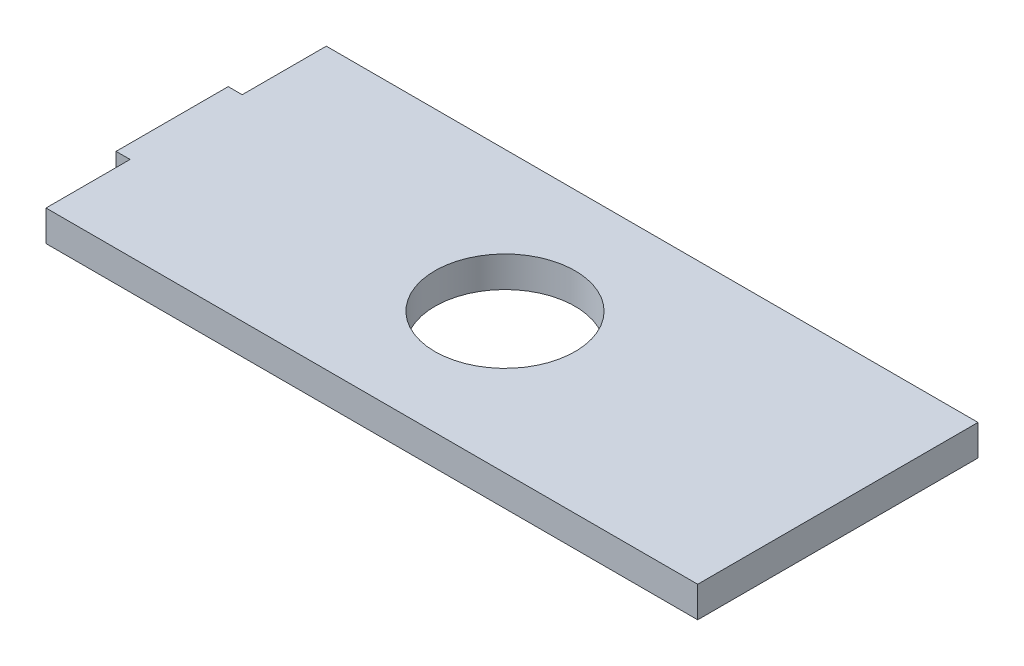
SolidWorks part; units mm, degrees
material "cardboard"
ref_plane "Front Plane" through (0, 0, 0) normal (0, 0, 1) x (1, 0, 0)
ref_plane "Top Plane" through (0, 0, 0) normal (0, 1, 0) x (1, 0, 0)
ref_plane "Right Plane" through (0, 0, 0) normal (1, 0, 0) x (0, 0, -1)
sketch "Sketch1" plane through (0, 0, 0) normal (0, 1, 0) x (1, 0, 0)
  line L0 (78.5546, 11.8659) -> (71.7044, 7.911)
  line L1 (104.0546, -12.1341) -> (110.9047, -8.1792)
  line L2 (119.2044, 7.911) -> (110.9047, 7.911)
  line L3 (119.2044, -8.1792) -> (110.9047, -8.1792)
  line L4 (71.7044, 7.911) -> (63.4047, 7.911)
  line L5 (126.0546, 11.8659) -> (119.2044, 7.911)
  line L6 (126.0546, -12.1341) -> (119.2044, -8.1792)
  line L7 (104.0546, 11.8659) -> (110.9047, 7.911)
  line L8 (126.0546, 11.8659) -> (138.8046, 11.8659)
  line L9 (126.0546, -12.1341) -> (162.8046, -12.1341)
  line L10 (56.5546, 11.8659) -> (63.4047, 7.911)
  line L11 (56.5546, -12.1341) -> (63.4047, -8.1792)
  line L12 (78.5546, -12.1341) -> (71.7044, -8.1792)
  line L13 (71.7044, -8.1792) -> (63.4047, -8.1792)
  line L14 (78.5546, 11.8659) -> (104.0546, 11.8659)
  line L15 (78.5546, -12.1341) -> (104.0546, -12.1341)
  line L16 (-11.1954, 77.6159) -> (-7.2405, 70.7658)
  line L17 (12.8046, 103.1159) -> (8.8496, 109.966)
  line L18 (-7.2405, 118.2658) -> (-7.2405, 109.966)
  line L19 (8.8496, 118.2658) -> (8.8496, 109.966)
  line L20 (-7.2405, 70.7658) -> (-7.2405, 62.466)
  line L21 (-11.1954, 125.1159) -> (-7.2405, 118.2658)
  line L22 (12.8046, 125.1159) -> (8.8496, 118.2658)
  line L23 (-11.1954, 103.1159) -> (-7.2405, 109.966)
  line L24 (-11.1954, 125.1159) -> (-11.1954, 137.8659)
  line L25 (12.8046, 125.1159) -> (12.8046, 161.8659)
  line L26 (-11.1954, 55.6159) -> (-7.2405, 62.466)
  line L27 (12.8046, 55.6159) -> (8.8496, 62.466)
  line L28 (12.8046, 77.6159) -> (8.8496, 70.7658)
  line L29 (8.8496, 70.7658) -> (8.8496, 62.466)
  line L30 (-11.1954, 77.6159) -> (-11.1954, 103.1159)
  line L31 (12.8046, 77.6159) -> (12.8046, 103.1159)
  line L32 (91.3046, 36.8659) -> (91.3046, 16.8659)
  line L33 (90.3046, 36.8659) -> (90.3046, 30.8659)
  line L34 (37.8046, 11.8659) -> (43.8046, 11.8659)
  line L35 (90.3046, 30.8659) -> (92.3046, 30.8659)
  line L36 (42.5546, 11.8659) -> (42.5546, 9.8659)
  line L37 (43.8046, 11.8659) -> (56.5546, 11.8659)
  line L38 (138.8046, 11.8659) -> (138.8046, -12.1341)
  line L39 (138.8046, 11.8659) -> (162.8046, 11.8659)
  line L40 (162.8046, 11.8659) -> (162.8046, 9.8659)
  line L41 (-27.6918, 14.2202) -> (0.8046, -14.2762)
  line L42 (-27.6918, 14.2202) -> (-13.5497, 28.3623)
  line L43 (0.8046, -14.2762) -> (14.9467, -0.1341)
  line L44 (-13.5497, 28.3623) -> (14.9467, -0.1341)
  line L45 (138.8046, 11.8659) -> (138.8046, 36.8659)
  line L46 (40.8046, 36.8659) -> (162.8046, 36.8659)
  line L47 (162.8046, 36.8659) -> (162.8046, 11.8659)
  line L48 (92.3046, 30.8659) -> (92.3046, 22.8659)
  line L49 (138.8046, 36.8659) -> (138.8046, 60.8659)
  line L50 (138.8046, 60.8659) -> (147.8046, 60.8659)
  line L51 (43.8046, 36.8659) -> (43.8046, 16.8659)
  line L52 (162.8046, 60.8659) -> (162.8046, 51.1879)
  line L53 (147.8046, 60.8659) -> (147.8046, 63.0659)
  line L54 (153.8046, 63.0659) -> (153.8046, 60.8659)
  line L55 (153.8046, 60.8659) -> (162.8046, 60.8659)
  line L56 (-58.1954, 137.8659) -> (-58.1954, 113.3659)
  line L57 (-38.1954, 113.3659) -> (-38.1954, 137.8659)
  line L58 (92.3046, 22.8659) -> (90.3046, 22.8659)
  line L59 (138.8046, -12.1341) -> (138.8046, -37.1341)
  line L60 (147.8046, -37.1341) -> (153.8046, -37.1341)
  line L61 (162.8046, -37.1341) -> (162.8046, -12.1341)
  line L62 (43.8046, -37.1341) -> (43.8046, -17.1341)
  line L63 (138.8046, -37.1341) -> (138.8046, -38.3141)
  line L64 (153.8046, -38.3141) -> (162.8046, -38.3141)
  line L65 (162.8046, -38.3141) -> (162.8046, -37.1341)
  line L66 (147.8046, -38.3141) -> (147.8046, -37.1341)
  line L67 (153.8046, -38.3141) -> (153.8046, -37.1341)
  line L68 (-37.3754, -138.1341) -> (-37.3754, -147.1341)
  line L69 (90.3046, 22.8659) -> (90.3046, 16.8659)
  line L70 (90.3046, 11.8659) -> (90.3046, 3.8659)
  line L71 (43.8046, -12.1341) -> (56.5546, -12.1341)
  line L72 (37.8046, -12.1341) -> (43.8046, -12.1341)
  line L73 (91.2784, 11.8659) -> (91.2784, -12.1341)
  line L74 (90.3046, 3.8659) -> (92.3046, 3.8659)
  line L75 (92.3046, 3.8659) -> (92.3046, -4.1341)
  line L76 (92.3046, -4.1341) -> (90.3046, -4.1341)
  line L77 (136.8046, 11.8659) -> (136.8046, 3.8659)
  line L78 (136.8046, 3.8659) -> (140.8046, 3.8659)
  line L79 (38.9846, 161.8659) -> (38.9846, 152.8659)
  line L80 (38.8046, 34.8659) -> (38.8046, 18.8659)
  line L81 (40.8046, 16.8659) -> (138.8046, 16.8659)
  line L82 (42.5546, 23.8659) -> (42.5546, 16.8659)
  line L83 (43.8046, 29.8659) -> (40.8046, 29.8659)
  line L84 (40.8046, 29.8659) -> (40.8046, 23.8659)
  line L85 (45.0546, 5.8659) -> (42.5546, 5.8659)
  line L86 (6.8046, -41.8841) -> (6.8046, -39.8841)
  line L87 (42.5546, -6.1341) -> (45.0546, -6.1341)
  line L88 (45.0546, 5.8659) -> (45.0546, -6.1341)
  line L89 (43.8046, 11.8659) -> (43.8046, 5.8659)
  line L90 (42.5546, 9.8659) -> (45.0546, 9.8659)
  line L91 (45.0546, 9.8659) -> (45.0546, 7.8659)
  line L92 (45.0546, 7.8659) -> (42.5546, 7.8659)
  line L93 (42.5546, 7.8659) -> (42.5546, 5.8659)
  line L94 (42.5546, -8.1341) -> (42.5546, -6.1341)
  line L95 (45.0546, -8.1341) -> (42.5546, -8.1341)
  line L96 (45.0546, -10.1341) -> (45.0546, -8.1341)
  line L97 (42.5546, -10.1341) -> (45.0546, -10.1341)
  line L98 (42.5546, -12.1341) -> (42.5546, -10.1341)
  line L99 (140.8046, 3.8659) -> (140.8046, -4.1341)
  line L100 (140.8046, -4.1341) -> (136.8046, -4.1341)
  line L101 (136.8046, -4.1341) -> (136.8046, -12.1341)
  line L102 (138.8046, 13.8659) -> (146.8046, 13.8659)
  line L103 (146.8046, 13.8659) -> (146.8046, 9.8659)
  line L104 (146.8046, 9.8659) -> (154.8046, 9.8659)
  line L105 (154.8046, 9.8659) -> (154.8046, 13.8659)
  line L106 (154.8046, 13.8659) -> (162.8046, 13.8659)
  line L107 (137.3046, 36.8659) -> (137.3046, 30.8659)
  line L108 (137.3046, 30.8659) -> (140.3046, 30.8659)
  line L109 (140.3046, 30.8659) -> (140.3046, 22.8659)
  line L110 (140.3046, 22.8659) -> (137.3046, 22.8659)
  line L111 (137.3046, 22.8659) -> (137.3046, 16.8659)
  line L112 (90.3046, -4.1341) -> (90.3046, -12.1341)
  line L113 (90.3046, -23.1341) -> (90.3046, -17.1341)
  line L114 (91.3046, -37.1341) -> (91.3046, -17.1341)
  line L115 (92.3046, -23.1341) -> (90.3046, -23.1341)
  line L116 (92.3046, -31.1341) -> (92.3046, -23.1341)
  line L117 (154.8046, -14.1341) -> (162.8046, -14.1341)
  line L118 (154.8046, -10.1341) -> (154.8046, -14.1341)
  line L119 (146.8046, -10.1341) -> (154.8046, -10.1341)
  line L120 (146.8046, -14.1341) -> (146.8046, -10.1341)
  line L121 (138.8046, -14.1341) -> (146.8046, -14.1341)
  line L122 (137.3046, -23.1341) -> (137.3046, -17.1341)
  line L123 (140.3046, -23.1341) -> (137.3046, -23.1341)
  line L124 (42.5546, 36.8659) -> (42.5546, 29.8659)
  line L125 (43.8046, 23.8659) -> (40.8046, 23.8659)
  line L126 (138.8046, -37.1341) -> (40.8046, -37.1341)
  line L127 (38.8046, -35.1341) -> (38.8046, -19.1341)
  line L128 (40.8046, -17.1341) -> (138.8046, -17.1341)
  line L129 (140.3046, -31.1341) -> (140.3046, -23.1341)
  line L130 (137.3046, -31.1341) -> (140.3046, -31.1341)
  line L131 (137.3046, -37.1341) -> (137.3046, -31.1341)
  line L132 (90.3046, -31.1341) -> (92.3046, -31.1341)
  line L133 (90.3046, -37.1341) -> (90.3046, -31.1341)
  line L134 (138.8046, 38.8659) -> (146.8046, 38.8659)
  line L135 (146.8046, 38.8659) -> (146.8046, 34.8659)
  line L136 (146.8046, 34.8659) -> (154.8046, 34.8659)
  line L137 (154.8046, 34.8659) -> (154.8046, 38.8659)
  line L138 (154.8046, 38.8659) -> (162.8046, 38.8659)
  line L139 (-43.6954, 133.6159) -> (-43.6954, 117.6159)
  line L140 (-55.1954, 133.6159) -> (-52.6954, 133.6159)
  line L141 (-55.1954, 133.6159) -> (-55.1954, 117.6159)
  line L142 (-55.1954, 117.6159) -> (-52.6954, 117.6159)
  line L143 (-52.6954, 133.6159) -> (-52.6954, 117.6159)
  line L144 (42.5546, -24.1341) -> (42.5546, -17.1341)
  line L145 (43.8046, -24.1341) -> (40.8046, -24.1341)
  line L146 (40.8046, -30.1341) -> (40.8046, -24.1341)
  line L147 (43.8046, -30.1341) -> (40.8046, -30.1341)
  line L148 (42.5546, -37.1341) -> (42.5546, -30.1341)
  line L149 (197.8046, 4.8659) -> (197.8046, -5.1341)
  line L150 (192.8046, 9.8659) -> (162.8046, 9.8659)
  line L151 (192.8046, -10.1341) -> (162.8046, -10.1341)
  line L152 (192.8046, 9.8659) -> (197.8046, 4.8659)
  line L153 (197.8046, -5.1341) -> (192.8046, -10.1341)
  line L154 (162.8046, -10.1341) -> (162.8046, -12.1341)
  line L155 (138.8046, 63.0659) -> (147.8046, 63.0659)
  line L156 (138.8046, 63.0659) -> (138.8046, 65.0659)
  line L157 (138.8046, 65.0659) -> (162.8046, 65.0659)
  line L158 (162.8046, 65.0659) -> (162.8046, 63.0659)
  line L159 (153.8046, 63.0659) -> (162.8046, 63.0659)
  line L160 (-41.1954, 117.6159) -> (-43.6954, 117.6159)
  line L161 (-41.1954, 133.6159) -> (-41.1954, 117.6159)
  line L162 (-41.1954, 133.6159) -> (-43.6954, 133.6159)
  line L163 (156.2046, 51.1879) -> (162.8046, 51.1879)
  line L164 (156.2046, 51.1879) -> (156.2046, 46.6879)
  line L165 (156.2046, 46.6879) -> (162.8046, 46.6879)
  line L166 (162.8046, 46.6879) -> (162.8046, 36.8659)
  line L167 (12.8046, -77.8841) -> (8.8496, -71.034)
  line L168 (-11.1954, -103.3841) -> (-7.2405, -110.2342)
  line L169 (8.8496, -118.534) -> (8.8496, -110.2342)
  line L170 (12.8046, -37.1341) -> (12.8046, -43.1341)
  line L171 (12.8046, -41.8841) -> (10.8046, -41.8841)
  line L172 (12.8046, -43.1341) -> (12.8046, -55.8841)
  line L173 (-7.2405, -118.534) -> (-7.2405, -110.2342)
  line L174 (8.8496, -71.034) -> (8.8496, -62.7342)
  line L175 (12.8046, -125.3841) -> (8.8496, -118.534)
  line L176 (-11.1954, -125.3841) -> (-7.2405, -118.534)
  line L177 (12.8046, -103.3841) -> (8.8496, -110.2342)
  line L178 (12.8046, -125.3841) -> (12.8046, -138.1341)
  line L179 (-11.1954, -125.3841) -> (-11.1954, -162.1341)
  line L180 (12.8046, -55.8841) -> (8.8496, -62.7342)
  line L181 (-11.1954, -55.8841) -> (-7.2405, -62.7342)
  line L182 (37.8046, -43.1341) -> (17.8046, -43.1341)
  line L183 (-11.1954, -77.8841) -> (-7.2405, -71.034)
  line L184 (-7.2405, -71.034) -> (-7.2405, -62.7342)
  line L185 (12.8046, -77.8841) -> (12.8046, -103.3841)
  line L186 (-11.1954, -77.8841) -> (-11.1954, -103.3841)
  line L187 (37.8046, -90.6341) -> (17.8046, -90.6341)
  line L188 (37.8046, -89.6341) -> (31.8046, -89.6341)
  line L189 (31.8046, -89.6341) -> (31.8046, -91.6341)
  line L190 (12.8046, -138.1341) -> (-11.1954, -138.1341)
  line L191 (12.8046, -138.1341) -> (12.8046, -162.1341)
  line L192 (12.8046, -162.1341) -> (10.8046, -162.1341)
  line L193 (12.8046, -138.1341) -> (37.8046, -138.1341)
  line L194 (37.8046, -40.1341) -> (37.8046, -162.1341)
  line L195 (-36.1954, -43.1341) -> (-16.1954, -43.1341)
  line L196 (37.8046, -162.1341) -> (12.8046, -162.1341)
  line L197 (31.8046, -91.6341) -> (23.8046, -91.6341)
  line L198 (37.8046, -138.1341) -> (61.8046, -138.1341)
  line L199 (61.8046, -138.1341) -> (61.8046, -147.1341)
  line L200 (61.8046, -162.1341) -> (52.1265, -162.1341)
  line L201 (61.8046, -147.1341) -> (64.0046, -147.1341)
  line L202 (64.0046, -153.1341) -> (61.8046, -153.1341)
  line L203 (61.8046, -153.1341) -> (61.8046, -162.1341)
  line L204 (-11.1954, -43.1341) -> (-11.1954, -55.8841)
  line L205 (-11.1954, -37.1341) -> (-11.1954, -43.1341)
  line L206 (23.8046, -91.6341) -> (23.8046, -89.6341)
  line L207 (-11.1954, -138.1341) -> (-36.1954, -138.1341)
  line L208 (-36.1954, -147.1341) -> (-36.1954, -153.1341)
  line L209 (38.9846, 146.8659) -> (38.9846, 137.8659)
  line L210 (35.8046, -38.1341) -> (19.8046, -38.1341)
  line L211 (17.8046, -40.1341) -> (17.8046, -138.1341)
  line L212 (24.8046, -41.8841) -> (17.8046, -41.8841)
  line L213 (30.8046, -43.1341) -> (30.8046, -40.1341)
  line L214 (30.8046, -40.1341) -> (24.8046, -40.1341)
  line L215 (6.8046, -44.3841) -> (6.8046, -41.8841)
  line L216 (-36.1954, -162.1341) -> (-11.1954, -162.1341)
  line L217 (-5.1954, -41.8841) -> (-5.1954, -44.3841)
  line L218 (6.8046, -44.3841) -> (-5.1954, -44.3841)
  line L219 (12.8046, -43.1341) -> (6.8046, -43.1341)
  line L220 (10.8046, -41.8841) -> (10.8046, -44.3841)
  line L221 (10.8046, -44.3841) -> (8.8046, -44.3841)
  line L222 (8.8046, -44.3841) -> (8.8046, -41.8841)
  line L223 (8.8046, -41.8841) -> (6.8046, -41.8841)
  line L224 (-7.1954, -41.8841) -> (-5.1954, -41.8841)
  line L225 (-7.1954, -44.3841) -> (-7.1954, -41.8841)
  line L226 (-9.1954, -44.3841) -> (-7.1954, -44.3841)
  line L227 (-9.1954, -41.8841) -> (-9.1954, -44.3841)
  line L228 (-11.1954, -41.8841) -> (-9.1954, -41.8841)
  line L229 (-36.1954, -138.1341) -> (-37.3754, -138.1341)
  line L230 (-37.3754, -153.1341) -> (-37.3754, -162.1341)
  line L231 (-37.3754, -162.1341) -> (-36.1954, -162.1341)
  line L232 (-37.3754, -147.1341) -> (-36.1954, -147.1341)
  line L233 (-37.3754, -153.1341) -> (-36.1954, -153.1341)
  line L234 (-161.1954, 38.0459) -> (-152.1954, 38.0459)
  line L235 (23.8046, -89.6341) -> (17.8046, -89.6341)
  line L236 (12.8046, -89.6341) -> (4.8046, -89.6341)
  line L237 (12.8046, -90.6079) -> (-11.1954, -90.6079)
  line L238 (4.8046, -89.6341) -> (4.8046, -91.6341)
  line L239 (4.8046, -91.6341) -> (-3.1954, -91.6341)
  line L240 (-3.1954, -91.6341) -> (-3.1954, -89.6341)
  line L241 (12.8046, -136.1341) -> (4.8046, -136.1341)
  line L242 (4.8046, -136.1341) -> (4.8046, -140.1341)
  line L243 (4.8046, -140.1341) -> (-3.1954, -140.1341)
  line L244 (-3.1954, -140.1341) -> (-3.1954, -136.1341)
  line L245 (-3.1954, -136.1341) -> (-11.1954, -136.1341)
  line L246 (14.8046, -138.1341) -> (14.8046, -146.1341)
  line L247 (14.8046, -146.1341) -> (10.8046, -146.1341)
  line L248 (10.8046, -146.1341) -> (10.8046, -154.1341)
  line L249 (10.8046, -154.1341) -> (14.8046, -154.1341)
  line L250 (14.8046, -154.1341) -> (14.8046, -162.1341)
  line L251 (37.8046, -136.6341) -> (31.8046, -136.6341)
  line L252 (31.8046, -136.6341) -> (31.8046, -139.6341)
  line L253 (31.8046, -139.6341) -> (23.8046, -139.6341)
  line L254 (37.8046, -41.8841) -> (30.8046, -41.8841)
  line L255 (24.8046, -43.1341) -> (24.8046, -40.1341)
  line L256 (-36.1954, -138.1341) -> (-36.1954, -40.1341)
  line L257 (-34.1954, -38.1341) -> (-18.1954, -38.1341)
  line L258 (-16.1954, -40.1341) -> (-16.1954, -138.1341)
  line L259 (23.8046, -139.6341) -> (23.8046, -136.6341)
  line L260 (23.8046, -136.6341) -> (17.8046, -136.6341)
  line L261 (-3.1954, -89.6341) -> (-11.1954, -89.6341)
  line L262 (-22.1954, -89.6341) -> (-16.1954, -89.6341)
  line L263 (-36.1954, -90.6341) -> (-16.1954, -90.6341)
  line L264 (-22.1954, -91.6341) -> (-22.1954, -89.6341)
  line L265 (-30.1954, -91.6341) -> (-22.1954, -91.6341)
  line L266 (-13.1954, -154.1341) -> (-13.1954, -162.1341)
  line L267 (-9.1954, -154.1341) -> (-13.1954, -154.1341)
  line L268 (-9.1954, -146.1341) -> (-9.1954, -154.1341)
  line L269 (-13.1954, -146.1341) -> (-9.1954, -146.1341)
  line L270 (-13.1954, -138.1341) -> (-13.1954, -146.1341)
  line L271 (-22.1954, -136.6341) -> (-16.1954, -136.6341)
  line L272 (-22.1954, -139.6341) -> (-22.1954, -136.6341)
  line L273 (-30.1954, -139.6341) -> (-22.1954, -139.6341)
  line L274 (-23.1954, -41.8841) -> (-16.1954, -41.8841)
  line L275 (-23.1954, -43.1341) -> (-23.1954, -40.1341)
  line L276 (-29.1954, -40.1341) -> (-23.1954, -40.1341)
  line L277 (-29.1954, -43.1341) -> (-29.1954, -40.1341)
  line L278 (-36.1954, -41.8841) -> (-29.1954, -41.8841)
  line L279 (-30.1954, -136.6341) -> (-30.1954, -139.6341)
  line L280 (-36.1954, -136.6341) -> (-30.1954, -136.6341)
  line L281 (-30.1954, -89.6341) -> (-30.1954, -91.6341)
  line L282 (-36.1954, -89.6341) -> (-30.1954, -89.6341)
  line L283 (39.8046, -138.1341) -> (39.8046, -146.1341)
  line L284 (39.8046, -146.1341) -> (35.8046, -146.1341)
  line L285 (35.8046, -146.1341) -> (35.8046, -154.1341)
  line L286 (35.8046, -154.1341) -> (39.8046, -154.1341)
  line L287 (39.8046, -154.1341) -> (39.8046, -162.1341)
  line L288 (5.8046, -197.1341) -> (-4.1954, -197.1341)
  line L289 (10.8046, -192.1341) -> (10.8046, -162.1341)
  line L290 (-9.1954, -192.1341) -> (-9.1954, -162.1341)
  line L291 (10.8046, -192.1341) -> (5.8046, -197.1341)
  line L292 (-4.1954, -197.1341) -> (-9.1954, -192.1341)
  line L293 (-9.1954, -162.1341) -> (-11.1954, -162.1341)
  line L294 (64.0046, -138.1341) -> (64.0046, -147.1341)
  line L295 (64.0046, -138.1341) -> (66.0046, -138.1341)
  line L296 (66.0046, -138.1341) -> (66.0046, -162.1341)
  line L297 (66.0046, -162.1341) -> (64.0046, -162.1341)
  line L298 (64.0046, -153.1341) -> (64.0046, -162.1341)
  line L299 (-36.1954, -12.1341) -> (-42.1954, -12.1341)
  line L300 (-40.9454, -12.1341) -> (-40.9454, -10.1341)
  line L301 (-42.1954, -12.1341) -> (-54.9454, -12.1341)
  line L302 (52.1265, -155.5341) -> (52.1265, -162.1341)
  line L303 (52.1265, -155.5341) -> (47.6265, -155.5341)
  line L304 (-42.1954, -37.1341) -> (-42.1954, -17.1341)
  line L305 (47.6265, -155.5341) -> (47.6265, -162.1341)
  line L306 (47.6265, -162.1341) -> (37.8046, -162.1341)
  line L307 (-76.9454, -12.1341) -> (-70.0953, -8.1792)
  line L308 (-102.4454, 11.8659) -> (-109.2956, 7.911)
  line L309 (-117.5953, -8.1792) -> (-109.2956, -8.1792)
  line L310 (-117.5953, 7.911) -> (-109.2956, 7.911)
  line L311 (-70.0953, -8.1792) -> (-61.7956, -8.1792)
  line L312 (-124.4454, -12.1341) -> (-117.5953, -8.1792)
  line L313 (-124.4454, 11.8659) -> (-117.5953, 7.911)
  line L314 (-102.4454, -12.1341) -> (-109.2956, -8.1792)
  line L315 (-124.4454, -12.1341) -> (-137.1954, -12.1341)
  line L316 (-42.1954, 36.8659) -> (-42.1954, 16.8659)
  line L317 (-124.4454, 11.8659) -> (-161.1954, 11.8659)
  line L318 (-54.9454, -12.1341) -> (-61.7956, -8.1792)
  line L319 (-54.9454, 11.8659) -> (-61.7956, 7.911)
  line L320 (-76.9454, 11.8659) -> (-70.0953, 7.911)
  line L321 (-70.0953, 7.911) -> (-61.7956, 7.911)
  line L322 (-76.9454, -12.1341) -> (-102.4454, -12.1341)
  line L323 (-76.9454, 11.8659) -> (-102.4454, 11.8659)
  line L324 (-89.6954, -37.1341) -> (-89.6954, -17.1341)
  line L325 (-42.1954, 11.8659) -> (-54.9454, 11.8659)
  line L326 (-36.1954, 11.8659) -> (-42.1954, 11.8659)
  line L327 (-88.6954, -37.1341) -> (-88.6954, -31.1341)
  line L328 (-88.6954, -31.1341) -> (-90.6954, -31.1341)
  line L329 (-137.1954, -12.1341) -> (-137.1954, 11.8659)
  line L330 (-137.1954, -12.1341) -> (-161.1954, -12.1341)
  line L331 (-161.1954, -12.1341) -> (-161.1954, -10.1341)
  line L332 (-137.1954, -12.1341) -> (-137.1954, -37.1341)
  line L333 (138.8046, -38.3141) -> (147.8046, -38.3141)
  line L334 (-37.1954, -35.1341) -> (-37.1954, -19.1341)
  line L335 (-39.1954, -17.1341) -> (-137.1954, -17.1341)
  line L336 (-40.9454, -24.1341) -> (-40.9454, -17.1341)
  line L337 (-42.1954, -30.1341) -> (-39.1954, -30.1341)
  line L338 (-39.1954, -30.1341) -> (-39.1954, -24.1341)
  line L339 (-43.4454, -6.1341) -> (-40.9454, -6.1341)
  line L340 (-39.1954, -37.1341) -> (-161.1954, -37.1341)
  line L341 (-40.9454, 5.8659) -> (-43.4454, 5.8659)
  line L342 (-43.4454, -6.1341) -> (-43.4454, 5.8659)
  line L343 (-42.1954, -12.1341) -> (-42.1954, -6.1341)
  line L344 (-40.9454, -10.1341) -> (-43.4454, -10.1341)
  line L345 (-43.4454, -10.1341) -> (-43.4454, -8.1341)
  line L346 (-43.4454, -8.1341) -> (-40.9454, -8.1341)
  line L347 (-40.9454, -8.1341) -> (-40.9454, -6.1341)
  line L348 (-40.9454, 7.8659) -> (-40.9454, 5.8659)
  line L349 (-43.4454, 7.8659) -> (-40.9454, 7.8659)
  line L350 (-43.4454, 9.8659) -> (-43.4454, 7.8659)
  line L351 (-40.9454, 9.8659) -> (-43.4454, 9.8659)
  line L352 (-40.9454, 11.8659) -> (-40.9454, 9.8659)
  line L353 (-161.1954, -37.1341) -> (-161.1954, -12.1341)
  line L354 (-90.6954, -31.1341) -> (-90.6954, -23.1341)
  line L355 (-137.1954, -37.1341) -> (-137.1954, -61.1341)
  line L356 (-137.1954, -61.1341) -> (-146.1954, -61.1341)
  line L357 (-161.1954, -61.1341) -> (-161.1954, -51.4561)
  line L358 (-146.1954, -61.1341) -> (-146.1954, -63.3341)
  line L359 (-152.1954, -63.3341) -> (-152.1954, -61.1341)
  line L360 (-152.1954, -61.1341) -> (-161.1954, -61.1341)
  line L361 (-90.6954, -23.1341) -> (-88.6954, -23.1341)
  line L362 (-137.1954, 11.8659) -> (-137.1954, 36.8659)
  line L363 (-146.1954, 36.8659) -> (-152.1954, 36.8659)
  line L364 (-161.1954, 36.8659) -> (-161.1954, 11.8659)
  line L365 (-137.1954, 36.8659) -> (-137.1954, 38.0459)
  line L366 (-161.1954, 38.0459) -> (-161.1954, 36.8659)
  line L367 (-146.1954, 38.0459) -> (-146.1954, 36.8659)
  line L368 (-152.1954, 38.0459) -> (-152.1954, 36.8659)
  line L369 (-146.1954, 38.0459) -> (-137.1954, 38.0459)
  line L370 (-88.6954, -23.1341) -> (-88.6954, -17.1341)
  line L371 (-88.6954, -12.1341) -> (-88.6954, -4.1341)
  line L372 (-89.6692, -12.1341) -> (-89.6692, 11.8659)
  line L373 (-88.6954, -4.1341) -> (-90.6954, -4.1341)
  line L374 (-40.9454, -37.1341) -> (-40.9454, -30.1341)
  line L375 (-42.1954, -24.1341) -> (-39.1954, -24.1341)
  line L376 (-137.1954, 36.8659) -> (-39.1954, 36.8659)
  line L377 (-37.1954, 34.8659) -> (-37.1954, 18.8659)
  line L378 (-39.1954, 16.8659) -> (-137.1954, 16.8659)
  line L379 (-90.6954, -4.1341) -> (-90.6954, 3.8659)
  line L380 (-90.6954, 3.8659) -> (-88.6954, 3.8659)
  line L381 (-135.1954, -12.1341) -> (-135.1954, -4.1341)
  line L382 (-135.1954, -4.1341) -> (-139.1954, -4.1341)
  line L383 (-139.1954, -4.1341) -> (-139.1954, 3.8659)
  line L384 (-139.1954, 3.8659) -> (-135.1954, 3.8659)
  line L385 (-135.1954, 3.8659) -> (-135.1954, 11.8659)
  line L386 (-137.1954, -14.1341) -> (-145.1954, -14.1341)
  line L387 (-145.1954, -14.1341) -> (-145.1954, -10.1341)
  line L388 (-145.1954, -10.1341) -> (-153.1954, -10.1341)
  line L389 (-153.1954, -10.1341) -> (-153.1954, -14.1341)
  line L390 (-153.1954, -14.1341) -> (-161.1954, -14.1341)
  line L391 (-135.6954, -37.1341) -> (-135.6954, -31.1341)
  line L392 (-36.1954, 90.3659) -> (-16.1954, 90.3659)
  line L393 (-36.1954, 89.3659) -> (-30.1954, 89.3659)
  line L394 (-40.9454, 23.8659) -> (-40.9454, 16.8659)
  line L395 (-42.1954, 23.8659) -> (-39.1954, 23.8659)
  line L396 (-39.1954, 29.8659) -> (-39.1954, 23.8659)
  line L397 (-42.1954, 29.8659) -> (-39.1954, 29.8659)
  line L398 (-40.9454, 36.8659) -> (-40.9454, 29.8659)
  line L399 (-135.6954, -31.1341) -> (-138.6954, -31.1341)
  line L400 (-138.6954, -31.1341) -> (-138.6954, -23.1341)
  line L401 (-138.6954, -23.1341) -> (-135.6954, -23.1341)
  line L402 (-135.6954, -23.1341) -> (-135.6954, -17.1341)
  line L403 (-88.6954, 3.8659) -> (-88.6954, 11.8659)
  line L404 (-88.6954, 22.8659) -> (-88.6954, 16.8659)
  line L405 (-89.6954, 36.8659) -> (-89.6954, 16.8659)
  line L406 (-90.6954, 22.8659) -> (-88.6954, 22.8659)
  line L407 (-90.6954, 30.8659) -> (-90.6954, 22.8659)
  line L408 (-153.1954, 13.8659) -> (-161.1954, 13.8659)
  line L409 (-153.1954, 9.8659) -> (-153.1954, 13.8659)
  line L410 (-145.1954, 9.8659) -> (-153.1954, 9.8659)
  line L411 (-145.1954, 13.8659) -> (-145.1954, 9.8659)
  line L412 (-137.1954, 13.8659) -> (-145.1954, 13.8659)
  line L413 (-135.6954, 22.8659) -> (-135.6954, 16.8659)
  line L414 (-138.6954, 22.8659) -> (-135.6954, 22.8659)
  line L415 (-138.6954, 30.8659) -> (-138.6954, 22.8659)
  line L416 (-135.6954, 30.8659) -> (-138.6954, 30.8659)
  line L417 (-135.6954, 36.8659) -> (-135.6954, 30.8659)
  line L418 (-88.6954, 30.8659) -> (-90.6954, 30.8659)
  line L419 (-88.6954, 36.8659) -> (-88.6954, 30.8659)
  line L420 (-137.1954, -39.1341) -> (-145.1954, -39.1341)
  line L421 (-145.1954, -39.1341) -> (-145.1954, -35.1341)
  line L422 (-145.1954, -35.1341) -> (-153.1954, -35.1341)
  line L423 (-153.1954, -35.1341) -> (-153.1954, -39.1341)
  line L424 (-153.1954, -39.1341) -> (-161.1954, -39.1341)
  line L425 (-11.1954, 41.6159) -> (-9.1954, 41.6159)
  line L426 (-30.1954, 89.3659) -> (-30.1954, 91.3659)
  line L427 (-11.1954, 137.8659) -> (12.8046, 137.8659)
  line L428 (-11.1954, 137.8659) -> (-11.1954, 161.8659)
  line L429 (-11.1954, 161.8659) -> (-9.1954, 161.8659)
  line L430 (-11.1954, 137.8659) -> (-36.1954, 137.8659)
  line L431 (-36.1954, 137.8659) -> (-36.1954, 161.8659)
  line L432 (-36.1954, 161.8659) -> (-11.1954, 161.8659)
  line L433 (-36.1954, 137.8659) -> (-36.1954, 42.8659)
  line L434 (-36.1954, 42.8659) -> (-16.1954, 42.8659)
  line L435 (-16.1954, 42.8659) -> (-16.1954, 137.8659)
  line L436 (-30.1954, 91.3659) -> (-22.1954, 91.3659)
  line L437 (-36.1954, 137.8659) -> (-60.1954, 137.8659)
  line L438 (-60.1954, 137.8659) -> (-60.1954, 146.8659)
  line L439 (-60.1954, 161.8659) -> (-50.5174, 161.8659)
  line L440 (-60.1954, 146.8659) -> (-62.3954, 146.8659)
  line L441 (-62.3954, 152.8659) -> (-60.1954, 152.8659)
  line L442 (-60.1954, 152.8659) -> (-60.1954, 161.8659)
  line L443 (-58.1954, 113.3659) -> (-38.1954, 113.3659)
  line L444 (37.8046, 42.8659) -> (17.8046, 42.8659)
  line L445 (-22.1954, 91.3659) -> (-22.1954, 89.3659)
  line L446 (37.8046, 137.8659) -> (37.8046, 42.8659)
  line L447 (17.8046, 42.8659) -> (17.8046, 137.8659)
  line L448 (12.8046, 137.8659) -> (37.8046, 137.8659)
  line L449 (37.8046, 146.8659) -> (37.8046, 152.8659)
  line L450 (37.8046, 161.8659) -> (12.8046, 161.8659)
  line L451 (12.8046, 36.8659) -> (12.8046, 55.6159)
  line L452 (37.8046, 137.8659) -> (38.9846, 137.8659)
  line L453 (38.9846, 161.8659) -> (37.8046, 161.8659)
  line L454 (38.9846, 146.8659) -> (37.8046, 146.8659)
  line L455 (38.9846, 152.8659) -> (37.8046, 152.8659)
  line L456 (-36.1954, 42.8659) -> (-36.1954, 39.8659)
  line L457 (-34.1954, 37.8659) -> (-18.1954, 37.8659)
  line L458 (-16.1954, 39.8659) -> (-16.1954, 42.8659)
  line L459 (35.8046, 37.8659) -> (19.8046, 37.8659)
  line L460 (17.8046, 39.8659) -> (17.8046, 42.8659)
  line L461 (-5.1954, 44.1159) -> (-5.1954, 41.6159)
  line L462 (-22.1954, 89.3659) -> (-16.1954, 89.3659)
  line L463 (6.8046, 41.6159) -> (6.8046, 44.1159)
  line L464 (-5.1954, 44.1159) -> (6.8046, 44.1159)
  line L465 (-11.1954, 42.8659) -> (-5.1954, 42.8659)
  line L466 (-9.1954, 41.6159) -> (-9.1954, 44.1159)
  line L467 (-9.1954, 44.1159) -> (-7.1954, 44.1159)
  line L468 (-7.1954, 44.1159) -> (-7.1954, 41.6159)
  line L469 (-7.1954, 41.6159) -> (-5.1954, 41.6159)
  line L470 (8.8046, 41.6159) -> (6.8046, 41.6159)
  line L471 (8.8046, 44.1159) -> (8.8046, 41.6159)
  line L472 (10.8046, 44.1159) -> (8.8046, 44.1159)
  line L473 (10.8046, 41.6159) -> (10.8046, 44.1159)
  line L474 (12.8046, 41.6159) -> (10.8046, 41.6159)
  line L475 (-11.1954, 89.3659) -> (-3.1954, 89.3659)
  line L476 (-11.1954, 90.3397) -> (12.8046, 90.3397)
  line L477 (-3.1954, 89.3659) -> (-3.1954, 91.3659)
  line L478 (-3.1954, 91.3659) -> (4.8046, 91.3659)
  line L479 (4.8046, 91.3659) -> (4.8046, 89.3659)
  line L480 (-11.1954, 135.8659) -> (-3.1954, 135.8659)
  line L481 (-3.1954, 135.8659) -> (-3.1954, 139.8659)
  line L482 (-3.1954, 139.8659) -> (4.8046, 139.8659)
  line L483 (4.8046, 139.8659) -> (4.8046, 135.8659)
  line L484 (4.8046, 135.8659) -> (12.8046, 135.8659)
  line L485 (-13.1954, 137.8659) -> (-13.1954, 145.8659)
  line L486 (-13.1954, 145.8659) -> (-9.1954, 145.8659)
  line L487 (-9.1954, 145.8659) -> (-9.1954, 153.8659)
  line L488 (-9.1954, 153.8659) -> (-13.1954, 153.8659)
  line L489 (-13.1954, 153.8659) -> (-13.1954, 161.8659)
  line L490 (-36.1954, 136.3659) -> (-30.1954, 136.3659)
  line L491 (-30.1954, 136.3659) -> (-30.1954, 139.3659)
  line L492 (-30.1954, 139.3659) -> (-22.1954, 139.3659)
  line L493 (-22.1954, 139.3659) -> (-22.1954, 136.3659)
  line L494 (-22.1954, 136.3659) -> (-16.1954, 136.3659)
  line L495 (4.8046, 89.3659) -> (12.8046, 89.3659)
  line L496 (23.8046, 89.3659) -> (17.8046, 89.3659)
  line L497 (37.8046, 90.3659) -> (17.8046, 90.3659)
  line L498 (23.8046, 91.3659) -> (23.8046, 89.3659)
  line L499 (31.8046, 91.3659) -> (23.8046, 91.3659)
  line L500 (-36.1954, 41.6159) -> (-29.1954, 41.6159)
  line L501 (30.8046, 39.8659) -> (24.8046, 39.8659)
  line L502 (24.8046, 41.6159) -> (17.8046, 41.6159)
  line L503 (-29.1954, 42.8659) -> (-29.1954, 39.8659)
  line L504 (-23.1954, 41.6159) -> (-16.1954, 41.6159)
  line L505 (14.8046, 153.8659) -> (14.8046, 161.8659)
  line L506 (10.8046, 153.8659) -> (14.8046, 153.8659)
  line L507 (10.8046, 145.8659) -> (10.8046, 153.8659)
  line L508 (14.8046, 145.8659) -> (10.8046, 145.8659)
  line L509 (14.8046, 137.8659) -> (14.8046, 145.8659)
  line L510 (23.8046, 136.3659) -> (17.8046, 136.3659)
  line L511 (23.8046, 139.3659) -> (23.8046, 136.3659)
  line L512 (31.8046, 139.3659) -> (23.8046, 139.3659)
  line L513 (31.8046, 136.3659) -> (31.8046, 139.3659)
  line L514 (37.8046, 136.3659) -> (31.8046, 136.3659)
  line L515 (31.8046, 89.3659) -> (31.8046, 91.3659)
  line L516 (37.8046, 89.3659) -> (31.8046, 89.3659)
  line L517 (12.8046, 36.8659) -> (21.769, 27.9014)
  line L518 (37.8046, -12.1341) -> (28.8401, -21.0986)
  line L519 (-11.1954, -37.1341) -> (-20.1599, -28.1696)
  line L520 (24.8046, 42.8659) -> (24.8046, 39.8659)
  line L521 (-23.1954, 42.8659) -> (-23.1954, 39.8659)
  line L522 (30.8046, 42.8659) -> (30.8046, 39.8659)
  line L523 (37.8046, 41.6159) -> (30.8046, 41.6159)
  line L524 (-38.1954, 137.8659) -> (-38.1954, 145.8659)
  line L525 (-38.1954, 145.8659) -> (-34.1954, 145.8659)
  line L526 (-34.1954, 145.8659) -> (-34.1954, 153.8659)
  line L527 (-34.1954, 153.8659) -> (-38.1954, 153.8659)
  line L528 (-38.1954, 153.8659) -> (-38.1954, 161.8659)
  line L529 (-58.1954, 136.3659) -> (-51.1954, 136.3659)
  line L530 (-51.1954, 136.3659) -> (-51.1954, 139.3659)
  line L531 (-51.1954, 139.3659) -> (-45.1954, 139.3659)
  line L532 (-45.1954, 139.3659) -> (-45.1954, 136.3659)
  line L533 (-45.1954, 136.3659) -> (-38.1954, 136.3659)
  line L534 (-11.1954, 36.8659) -> (-11.1954, 55.6159)
  line L535 (43.8046, -6.1341) -> (43.8046, -12.1341)
  line L536 (6.8046, 42.8659) -> (12.8046, 42.8659)
  line L537 (-42.1954, 5.8659) -> (-42.1954, 11.8659)
  line L538 (-5.1954, -43.1341) -> (-11.1954, -43.1341)
  line L539 (-4.1954, 196.8659) -> (5.8046, 196.8659)
  line L540 (-9.1954, 191.8659) -> (-9.1954, 161.8659)
  line L541 (10.8046, 191.8659) -> (10.8046, 161.8659)
  line L542 (-9.1954, 191.8659) -> (-4.1954, 196.8659)
  line L543 (5.8046, 196.8659) -> (10.8046, 191.8659)
  line L544 (134.5546, 55.8659) -> (118.5546, 55.8659)
  line L545 (134.5546, 55.8659) -> (134.5546, 53.3659)
  line L546 (-196.1954, -5.1341) -> (-196.1954, 4.8659)
  line L547 (-191.1954, -10.1341) -> (-161.1954, -10.1341)
  line L548 (-191.1954, 9.8659) -> (-161.1954, 9.8659)
  line L549 (-191.1954, -10.1341) -> (-196.1954, -5.1341)
  line L550 (-196.1954, 4.8659) -> (-191.1954, 9.8659)
  line L551 (-161.1954, 9.8659) -> (-161.1954, 11.8659)
  line L552 (-137.1954, -63.3341) -> (-146.1954, -63.3341)
  line L553 (-137.1954, -63.3341) -> (-137.1954, -65.3341)
  line L554 (-137.1954, -65.3341) -> (-161.1954, -65.3341)
  line L555 (-161.1954, -65.3341) -> (-161.1954, -63.3341)
  line L556 (10.8046, 161.8659) -> (12.8046, 161.8659)
  line L557 (-152.1954, -63.3341) -> (-161.1954, -63.3341)
  line L558 (134.5546, 53.3659) -> (118.5546, 53.3659)
  line L559 (118.5546, 55.8659) -> (118.5546, 53.3659)
  line L560 (134.5546, 44.3659) -> (118.5546, 44.3659)
  line L561 (134.5546, 41.8659) -> (134.5546, 44.3659)
  line L562 (134.5546, 41.8659) -> (118.5546, 41.8659)
  line L563 (118.5546, 41.8659) -> (118.5546, 44.3659)
  line L564 (137.3046, 58.8659) -> (137.3046, 51.8659)
  line L565 (137.3046, 51.8659) -> (140.3046, 51.8659)
  line L566 (-154.5954, -51.4561) -> (-161.1954, -51.4561)
  line L567 (-154.5954, -51.4561) -> (-154.5954, -46.9561)
  line L568 (-154.5954, -46.9561) -> (-161.1954, -46.9561)
  line L569 (-62.3954, 137.8659) -> (-62.3954, 146.8659)
  line L570 (-62.3954, 137.8659) -> (-64.3954, 137.8659)
  line L571 (-64.3954, 137.8659) -> (-64.3954, 161.8659)
  line L572 (-64.3954, 161.8659) -> (-62.3954, 161.8659)
  line L573 (-62.3954, 152.8659) -> (-62.3954, 161.8659)
  line L574 (-161.1954, -46.9561) -> (-161.1954, -37.1341)
  line L575 (140.3046, 51.8659) -> (140.3046, 45.8659)
  line L576 (-45.5575, 123.7107) -> (-46.6954, 123.7107)
  line L577 (-50.8334, 127.752) -> (-49.6954, 127.752)
  line L578 (-50.8334, 127.752) -> (-50.8334, 123.7107)
  line L579 (-50.8334, 123.7107) -> (-49.6954, 123.7107)
  line L580 (-49.6954, 127.752) -> (-49.6954, 123.7107)
  line L581 (-46.6954, 127.752) -> (-46.6954, 123.7107)
  line L582 (-45.5575, 127.752) -> (-46.6954, 127.752)
  line L583 (-45.5575, 127.752) -> (-45.5575, 123.7107)
  line L584 (140.3046, 45.8659) -> (137.3046, 45.8659)
  line L585 (137.3046, 45.8659) -> (137.3046, 38.8659)
  line L586 (114.3046, 38.8659) -> (138.8046, 38.8659)
  line L587 (114.3046, 58.8659) -> (114.3046, 38.8659)
  line L588 (138.8046, 58.8659) -> (114.3046, 58.8659)
  line L589 (56.8046, -133.8841) -> (56.8046, -117.8841)
  line L590 (56.8046, -133.8841) -> (54.3046, -133.8841)
  line L591 (-50.5174, 155.2659) -> (-50.5174, 161.8659)
  line L592 (-50.5174, 155.2659) -> (-46.0174, 155.2659)
  line L593 (-46.0174, 155.2659) -> (-46.0174, 161.8659)
  line L594 (-46.0174, 161.8659) -> (-36.1954, 161.8659)
  line L595 (54.3046, -133.8841) -> (54.3046, -117.8841)
  line L596 (56.8046, -117.8841) -> (54.3046, -117.8841)
  line L597 (-13.0888, 34.9725) -> (-11.1954, 36.8659)
  line L598 (-20.1599, 34.9725) -> (-22.2812, 37.0938)
  line L599 (-34.302, 20.8304) -> (-36.4233, 22.9517)
  line L600 (-36.4233, 22.9517) -> (-22.2812, 37.0938)
  line L601 (6.8046, -39.8841) -> (-5.1954, -39.8841)
  line L602 (42.5546, 5.8659) -> (40.5546, 5.8659)
  line L603 (-5.1954, -41.8841) -> (-5.1954, -39.8841)
  line L604 (42.5546, -6.1341) -> (40.5546, -6.1341)
  line L605 (40.5546, 5.8659) -> (40.5546, -6.1341)
  line L606 (-40.9454, -6.1341) -> (-38.9454, -6.1341)
  line L607 (-38.9454, -6.1341) -> (-38.9454, 5.8659)
  line L608 (-40.9454, 5.8659) -> (-38.9454, 5.8659)
  line L609 (-5.1954, 41.6159) -> (-5.1954, 39.6159)
  line L610 (-5.1954, 39.6159) -> (6.8046, 39.6159)
  line L611 (6.8046, 41.6159) -> (6.8046, 39.6159)
  line L612 (-36.1954, 11.8659) -> (-34.302, 13.7593)
  line L613 (-29.1954, 39.8659) -> (-23.1954, 39.8659)
  line L614 (26.7188, -18.9772) -> (19.6477, -26.0483)
  line L615 (19.6477, 25.7801) -> (26.7188, 18.709)
  line L616 (26.7188, 18.709) -> (28.8401, 20.8304)
  line L617 (45.3046, -133.8841) -> (45.3046, -117.8841)
  line L618 (42.8046, -133.8841) -> (45.3046, -133.8841)
  line L619 (42.8046, -133.8841) -> (42.8046, -117.8841)
  line L620 (42.8046, -117.8841) -> (45.3046, -117.8841)
  line L621 (59.8046, -136.6341) -> (52.8046, -136.6341)
  line L622 (52.8046, -136.6341) -> (52.8046, -139.6341)
  line L623 (52.8046, -139.6341) -> (46.8046, -139.6341)
  line L624 (46.8046, -139.6341) -> (46.8046, -136.6341)
  line L625 (46.8046, -136.6341) -> (39.8046, -136.6341)
  line L626 (39.8046, -113.6341) -> (39.8046, -138.1341)
  line L627 (59.8046, -113.6341) -> (39.8046, -113.6341)
  line L628 (59.8046, -138.1341) -> (59.8046, -113.6341)
  line L629 (-132.9454, -56.1341) -> (-116.9454, -56.1341)
  line L630 (-132.9454, -56.1341) -> (-132.9454, -53.6341)
  line L631 (-132.9454, -53.6341) -> (-116.9454, -53.6341)
  line L632 (-116.9454, -56.1341) -> (-116.9454, -53.6341)
  line L633 (-132.9454, -44.6341) -> (-116.9454, -44.6341)
  line L634 (-132.9454, -42.1341) -> (-132.9454, -44.6341)
  line L635 (-132.9454, -42.1341) -> (-116.9454, -42.1341)
  line L636 (-116.9454, -42.1341) -> (-116.9454, -44.6341)
  line L637 (-135.6954, -59.1341) -> (-135.6954, -52.1341)
  line L638 (-135.6954, -52.1341) -> (-138.6954, -52.1341)
  line L639 (-138.6954, -52.1341) -> (-138.6954, -46.1341)
  line L640 (-138.6954, -46.1341) -> (-135.6954, -46.1341)
  line L641 (-135.6954, -46.1341) -> (-135.6954, -39.1341)
  line L642 (-112.6954, -39.1341) -> (-137.1954, -39.1341)
  line L643 (-112.6954, -59.1341) -> (-112.6954, -39.1341)
  line L644 (-137.1954, -59.1341) -> (-112.6954, -59.1341)
  line L645 (128.6907, 51.5038) -> (124.6494, 51.5038)
  line L646 (128.6907, 51.5038) -> (128.6907, 50.3659)
  line L647 (128.6907, 50.3659) -> (124.6494, 50.3659)
  line L648 (124.6494, 51.5038) -> (124.6494, 50.3659)
  line L649 (128.6907, 47.3659) -> (124.6494, 47.3659)
  line L650 (19.6477, 25.7801) -> (21.769, 27.9014)
  line L651 (128.6907, 46.228) -> (128.6907, 47.3659)
  line L652 (128.6907, 46.228) -> (124.6494, 46.228)
  line L653 (124.6494, 46.228) -> (124.6494, 47.3659)
  line L654 (52.4425, -128.0202) -> (52.4425, -123.9789)
  line L655 (52.4425, -128.0202) -> (51.3046, -128.0202)
  line L656 (51.3046, -128.0202) -> (51.3046, -123.9789)
  line L657 (52.4425, -123.9789) -> (51.3046, -123.9789)
  line L658 (48.3046, -128.0202) -> (48.3046, -123.9789)
  line L659 (47.1666, -128.0202) -> (48.3046, -128.0202)
  line L660 (47.1666, -128.0202) -> (47.1666, -123.9789)
  line L661 (47.1666, -123.9789) -> (48.3046, -123.9789)
  line L662 (-127.0815, -51.772) -> (-123.0402, -51.772)
  line L663 (-127.0815, -51.772) -> (-127.0815, -50.6341)
  line L664 (-127.0815, -50.6341) -> (-123.0402, -50.6341)
  line L665 (-123.0402, -51.772) -> (-123.0402, -50.6341)
  line L666 (-127.0815, -47.6341) -> (-123.0402, -47.6341)
  line L667 (-127.0815, -46.4962) -> (-127.0815, -47.6341)
  line L668 (-127.0815, -46.4962) -> (-123.0402, -46.4962)
  line L669 (-123.0402, -46.4962) -> (-123.0402, -47.6341)
  line L670 (28.8401, 20.8304) -> (37.8046, 11.8659)
  line L671 (19.6477, -26.0483) -> (21.769, -28.1696)
  line L672 (26.7188, -18.9772) -> (28.8401, -21.0986)
  line L673 (-18.0386, -26.0483) -> (-25.1096, -18.9772)
  line L674 (-25.1096, -18.9772) -> (-27.231, -21.0986)
  line L675 (-18.0386, -26.0483) -> (-20.1599, -28.1696)
  line L676 (21.769, -28.1696) -> (12.8046, -37.1341)
  line L677 (-27.231, -21.0986) -> (-36.1954, -12.1341)
  line L678 (37.8046, 42.8659) -> (37.8046, 39.8659)
  circle A0 centre (157.5221, 42.1484) radius 1.5
  circle A1 centre (144.0871, 55.5834) radius 1.5
  circle A2 centre (156.4614, 54.5228) radius 1.5
  circle A3 centre (145.1477, 43.209) radius 1.5
  circle A4 centre (150.8046, 48.8659) radius 3.1
  circle A5 centre (150.8046, 24.3659) radius 5
  circle A6 centre (150.8046, -24.6341) radius 5
  circle A7 centre (67.5546, 26.8659) radius 5
  circle A8 centre (114.8052, 26.8659) radius 5
  circle A9 centre (67.5546, -27.1341) radius 5
  circle A10 centre (114.8052, -27.1341) radius 5
  circle A11 centre (150.8046, -0.1341) radius 7
  circle A12 centre (43.0871, -156.8516) radius 1.5
  circle A13 centre (56.5221, -143.4166) radius 1.5
  circle A14 centre (55.4614, -155.791) radius 1.5
  circle A15 centre (44.1477, -144.4772) radius 1.5
  circle A16 centre (49.8046, -150.1341) radius 3.1
  circle A17 centre (25.3046, -150.1341) radius 5
  circle A18 centre (-41.4779, 156.5834) radius 1.5
  circle A19 centre (-54.9129, 143.1484) radius 1.5
  circle A20 centre (-53.8523, 155.5228) radius 1.5
  circle A21 centre (-42.5386, 144.209) radius 1.5
  circle A22 centre (-48.1954, 149.8659) radius 3.1
  circle A23 centre (-23.6954, -150.1341) radius 5
  circle A24 centre (27.8046, -66.8841) radius 5
  circle A25 centre (27.8046, -114.1347) radius 5
  circle A26 centre (-26.1954, -66.8841) radius 5
  circle A27 centre (-26.1954, -114.1347) radius 5
  circle A28 centre (0.8046, -150.1341) radius 7
  circle A29 centre (-155.9129, -42.4166) radius 1.5
  circle A30 centre (-23.6954, 149.8659) radius 5
  circle A31 centre (25.3046, 149.8659) radius 5
  circle A32 centre (-142.4779, -55.8516) radius 1.5
  circle A33 centre (-154.8523, -54.791) radius 1.5
  circle A34 centre (-143.5386, -43.4772) radius 1.5
  circle A35 centre (-149.1954, -49.1341) radius 3.1
  circle A36 centre (-149.1954, -24.6341) radius 5
  circle A37 centre (-149.1954, 24.3659) radius 5
  circle A38 centre (-65.9454, -27.1341) radius 5
  circle A39 centre (-113.196, -27.1341) radius 5
  circle A40 centre (-65.9454, 26.8659) radius 5
  circle A41 centre (-113.196, 26.8659) radius 5
  circle A42 centre (-149.1954, -0.1341) radius 7
  circle A43 centre (-26.1954, 66.6159) radius 5
  circle A44 centre (-26.1954, 113.8665) radius 5
  circle A45 centre (27.8046, 66.6159) radius 5
  circle A46 centre (27.8046, 113.8665) radius 5
  arc A47 (40.8046, 36.8659) -> (38.8046, 34.8659) centre (40.8046, 34.8659) ccw
  arc A48 (38.8046, 18.8659) -> (40.8046, 16.8659) centre (40.8046, 18.8659) ccw
  arc A49 (-18.1954, 37.8659) -> (-16.1954, 39.8659) centre (-18.1954, 39.8659) ccw
  arc A50 (-36.1954, 39.8659) -> (-34.1954, 37.8659) centre (-34.1954, 39.8659) ccw
  arc A51 (37.8046, 39.8659) -> (35.8046, 37.8659) centre (35.8046, 39.8659) cw
  arc A52 (19.8046, 37.8659) -> (17.8046, 39.8659) centre (19.8046, 39.8659) cw
  arc A53 (40.8046, -37.1341) -> (38.8046, -35.1341) centre (40.8046, -35.1341) cw
  arc A54 (38.8046, -19.1341) -> (40.8046, -17.1341) centre (40.8046, -19.1341) cw
  arc A55 (37.8046, -40.1341) -> (35.8046, -38.1341) centre (35.8046, -40.1341) ccw
  arc A56 (19.8046, -38.1341) -> (17.8046, -40.1341) centre (19.8046, -40.1341) ccw
  arc A57 (-36.1954, -40.1341) -> (-34.1954, -38.1341) centre (-34.1954, -40.1341) cw
  arc A58 (-18.1954, -38.1341) -> (-16.1954, -40.1341) centre (-18.1954, -40.1341) cw
  arc A59 (-39.1954, -37.1341) -> (-37.1954, -35.1341) centre (-39.1954, -35.1341) ccw
  arc A60 (-37.1954, -19.1341) -> (-39.1954, -17.1341) centre (-39.1954, -19.1341) ccw
  arc A61 (-39.1954, 36.8659) -> (-37.1954, 34.8659) centre (-39.1954, 34.8659) cw
  arc A62 (-37.1954, 18.8659) -> (-39.1954, 16.8659) centre (-39.1954, 18.8659) cw
  arc A63 (-13.0888, 34.9725) -> (-20.1599, 34.9725) centre (-16.6244, 38.508) cw
  arc A64 (-34.302, 20.8304) -> (-34.302, 13.7593) centre (-37.8376, 17.2948) cw
  circle A65 centre (0.8046, 149.8659) radius 7
  point P194 (0.8046, -0.1341)
  point P589 (0.8046, -0.1341)
  point P595 (0.8046, -0.1341)
  point P596 (0.8046, -0.1341)
  point P601 (0.8046, -0.1341)
  point P604 (0.8046, -0.1341)
  point P629 (0.8046, -0.1341)
  point P660 (0.8046, -0.1341)
  point P686 (0.8046, -0.1341)
  point P715 (0.8046, -0.1341)
  point P716 (0.8046, -0.1341)
  point P740 (0.8046, -0.1341)
  point P743 (0.8046, -0.1341)
  point P783 (0.8046, -0.1341)
  point P809 (0.8046, -0.1341)
  point P816 (0.8046, -0.1341)
  point P829 (0.8046, -0.1341)
  point P860 (0.8046, -0.1341)
  point P885 (0.8046, -0.1341)
  point P890 (0.8046, -0.1341)
  point P910 (0.8046, -0.1341)
extrude "Boss-Extrude1" add sketch "Sketch1" along normal blind 2.2 contours L370 L361 L324 L328 L327 L340 L304 L335 A38 region at (-89.1954, 0, 23.6495)
